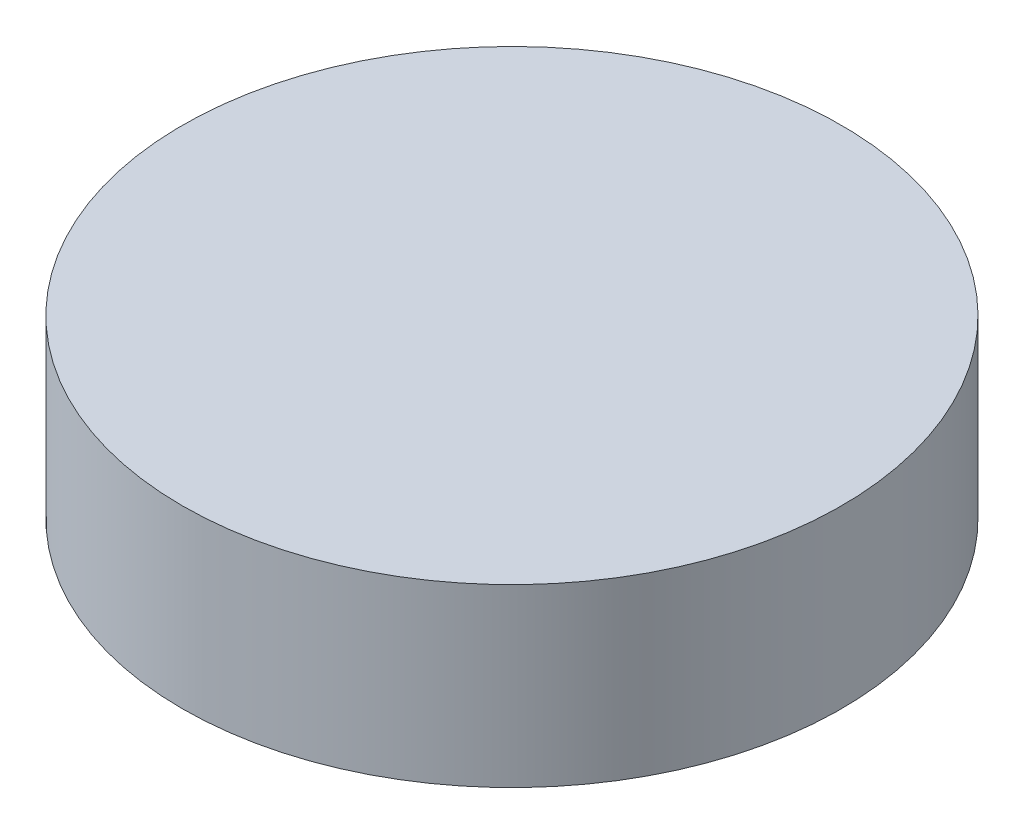
SolidWorks part; units mm, degrees
ref_plane "Front Plane" through (0, 0, 0) normal (0, 0, 1) x (1, 0, 0)
ref_plane "Top Plane" through (0, 0, 0) normal (0, 1, 0) x (1, 0, 0)
ref_plane "Right Plane" through (0, 0, 0) normal (1, 0, 0) x (0, 0, -1)
sketch "Sketch1" plane through (0, 0, 0) normal (0, 1, 0) x (1, 0, 0)
  circle A0 centre (0, 0) radius 37.5
  dimension "D1" = 75
extrude "Boss-Extrude1" add sketch "Sketch1" along normal blind 20
